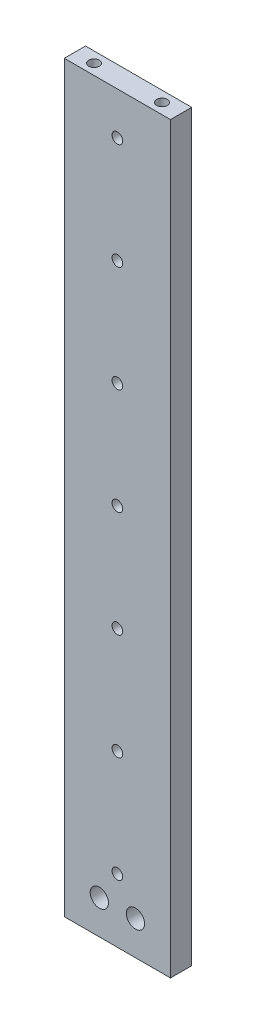
SolidWorks part; units mm, degrees
material "1060 Legierung"
ref_plane "Ebene vorne" through (0, 0, 0) normal (0, 0, 1) x (1, 0, 0)
ref_plane "Ebene oben" through (0, 0, 0) normal (0, 1, 0) x (1, 0, 0)
ref_plane "Ebene rechts" through (0, 0, 0) normal (1, 0, 0) x (0, 0, -1)
sketch "Skizze1" plane through (0, 0, 0) normal (1, 0, 0) x (0, 0, -1)
  line L0 (0, 0) -> (5, 0)
  line L3 (5, 0) -> (5, 175)
  line L4 (5, 175) -> (0, 175)
  line L5 (0, 175) -> (0, 0)
  dimension "D1" = 5
  dimension "D2" = 175
extrude "Aufsatz-Linear austragen1" add sketch "Skizze1" along normal blind 12.5 and the other way blind 12.5
hole_wizard "M3 Gewindebohrung3" positions "Skizze8" profile "Skizze9" tap size "M3" standard "DIN" end condition through all
sketch "Skizze8" plane through (0, 0, -5) normal (0, 0, -1) x (-1, 0, 0)
  line L3 (12.5, 175) -> (-12.5, 175) construction
  line L4 (0, 175) -> (0, 0) construction
  point P26 (0, 165)
  point P61 (0, 140)
  point P62 (0, 115)
  point P63 (0, 90)
  point P64 (0, 65)
  point P65 (0, 40)
  point P66 (0, 15)
  dimension "D1" = 10
  dimension "D2" = 7
  dimension "D3" = 25
sketch "Skizze9" plane through (0, 15, -5) normal (1, 0, 0) x (0, 1, 0)
  line L0 (0, 0) -> (0, 5)
  line L1 (0, 5) -> (1.25, 5)
  line L2 (1.25, 5) -> (1.25, 0)
  line L5 (1.25, 0) -> (0, 0)
  line L11 (0, -6.35) -> (0, 107.95) construction
  dimension "Nenndurchmesser (Haupt)" = 2.5
  dimension "Bohrungstiefe" = 5
hole_wizard "M3 Gewindebohrung1" positions "Skizze10" profile "Skizze11" tap size "M3" standard "DIN"
sketch "Skizze10" plane through (0, 175, 0) normal (0, 1, 0) x (1, 0, 0)
  line L0 (0, 0) -> (0, 5) construction
  line L1 (-12.5, 5) -> (12.5, 5) construction
  line L2 (-12.5, 5) -> (-12.5, 0) construction
  point P19 (-8, 2.5)
  point P21 (8, 2.5)
  point P28 (-12.5, 2.5)
  dimension "D1" = 16
sketch "Skizze11" plane through (8, 175, -2.5) normal (1, 0, 0) x (0, 0, 1)
  line L0 (0, 0) -> (0, 9.2511)
  line L1 (0, 9.2511) -> (1.25, 8.5)
  line L2 (1.25, 8.5) -> (1.25, 0)
  line L5 (1.25, 0) -> (0, 0)
  line L10 (0, 9.2511) -> (-1.25, 8.5) construction
  line L11 (0, -6.35) -> (0, 107.95) construction
  dimension "Bohrerdurchmesser" = 2.5
  dimension "Bohrungstiefe" = 8.5
  dimension "Spitzenwinkel" = 118
cosmetic thread "Bohrungsgewinde1" parameters "D1"=6, "D2"=3
cosmetic thread "Bohrungsgewinde2" parameters "D1"=6, "D2"=3
hole_wizard "M3 Gewindebohrung2" positions "Skizze13" profile "Skizze14" tap size "M3" standard "DIN"
sketch "Skizze13" plane through (0, 0, 0) normal (0, -1, 0) x (-1, 0, 0)
  line L0 (0, 0) -> (0, 5) construction
  line L2 (12.5, 5) -> (-12.5, 5) construction
  point P0 (8, 2.5)
  point P4 (-8, 2.5)
  dimension "D1" = 16
  dimension "D2" = 2.5
sketch "Skizze14" plane through (-8, 0, -2.5) normal (1, 0, 0) x (0, 0, -1)
  line L0 (0, 0) -> (0, 9.2511)
  line L1 (0, 9.2511) -> (1.25, 8.5)
  line L2 (1.25, 8.5) -> (1.25, 0)
  line L5 (1.25, 0) -> (0, 0)
  line L10 (0, 9.2511) -> (-1.25, 8.5) construction
  line L11 (0, -6.35) -> (0, 107.95) construction
  dimension "Bohrerdurchmesser" = 2.5
  dimension "Bohrungstiefe" = 8.5
  dimension "Spitzenwinkel" = 118
cosmetic thread "Bohrungsgewinde3" parameters "D1"=6, "D2"=3
cosmetic thread "Bohrungsgewinde4" parameters "D1"=6, "D2"=3
hole_wizard "Durchgangsloch für M41" positions "Skizze15" profile "Skizze16" hole size "M4" standard "DIN" end condition up to next
sketch "Skizze15" plane through (0, 0, -5) normal (0, 0, -1) x (-1, 0, 0)
  line L1 (0, 0) -> (0, 175) construction
  line L2 (12.5, 175) -> (-12.5, 175) construction
  line L4 (12.5, 0) -> (-12.5, 0) construction
  point P0 (-4.25, 8)
  point P4 (4.25, 8)
  dimension "D2" = 8
  dimension "D3" = 8.5
sketch "Skizze16" plane through (4.25, 8, -5) normal (1, 0, 0) x (0, 1, 0)
  line L0 (0, 0) -> (0, 5)
  line L1 (0, 5) -> (2.15, 5)
  line L2 (2.15, 5) -> (2.15, 0)
  line L5 (2.15, 0) -> (0, 0)
  line L11 (0, -6.35) -> (0, 107.95) construction
  dimension "Bohrerdurchmesser" = 4.3
  dimension "Bohrungstiefe" = 5
